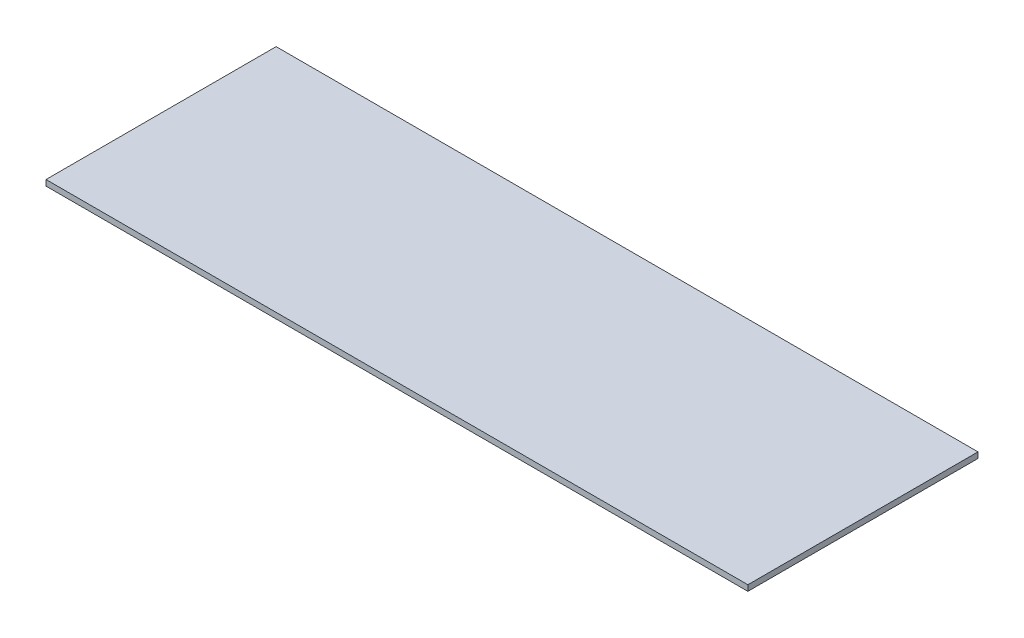
SolidWorks part; units mm, degrees
material "Oak"
ref_plane "Front Plane" through (0, 0, 0) normal (0, 0, 1) x (1, 0, 0)
ref_plane "Top Plane" through (0, 0, 0) normal (0, 1, 0) x (1, 0, 0)
ref_plane "Right Plane" through (0, 0, 0) normal (1, 0, 0) x (0, 0, -1)
sketch "Sketch1" plane through (0, 0, 0) normal (0, 1, 0) x (1, 0, 0)
  line L1 (-73.2022, 369.585) -> (1146.7978, 369.585)
  line L2 (-73.2022, 369.585) -> (-73.2022, -30.415)
  line L3 (-73.2022, -30.415) -> (1146.7978, -30.415)
  line L4 (1146.7978, 369.585) -> (1146.7978, -30.415)
extrude "Boss-Extrude1" add sketch "Sketch1" along normal blind 10 contours L2 L3 L4 L1
